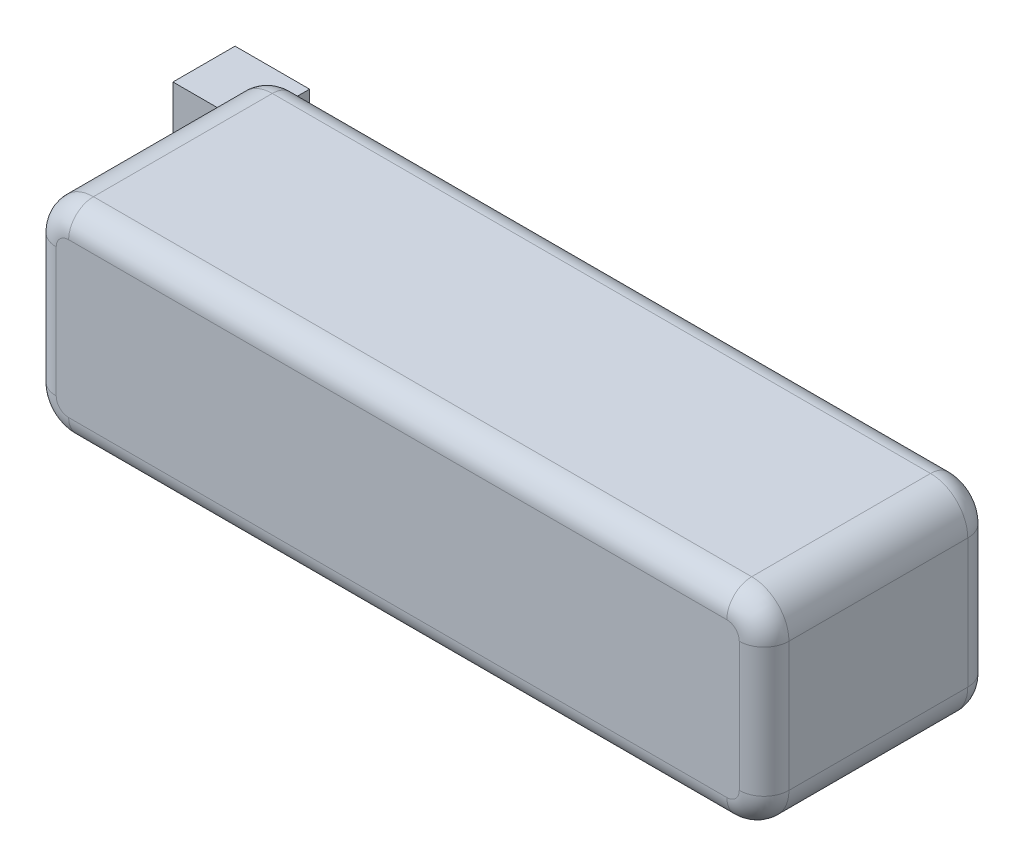
SolidWorks part; units mm, degrees
material "Polyurethane Foam Flexible"
ref_plane "Front Plane" through (0, 0, 0) normal (0, 0, 1) x (1, 0, 0)
ref_plane "Top Plane" through (0, 0, 0) normal (0, 1, 0) x (1, 0, 0)
ref_plane "Right Plane" through (0, 0, 0) normal (1, 0, 0) x (0, 0, -1)
sketch "Sketch1" plane through (0, 0, 0) normal (0, 1, 0) x (1, 0, 0)
  line L1 (0, 0) -> (74.93, 0)
  line L2 (0, 0) -> (0, -23.368)
  line L3 (0, -23.368) -> (74.93, -23.368)
  line L4 (74.93, 0) -> (74.93, -23.368)
  dimension "D1" = 74.93
  dimension "D2" = 23.368
extrude "Boss-Extrude1" add sketch "Sketch1" along normal blind 20.828
sketch "Sketch2" plane through (0, 0, 0) normal (-1, 0, 0) x (0, 0, 1)
  line L0 (0, 20.828) -> (0, 0) construction
  line L1 (0, 15.494) -> (1.27, 15.494)
  line L2 (0, 15.494) -> (0, 5.334)
  line L3 (0, 5.334) -> (1.27, 5.334)
  line L4 (1.27, 15.494) -> (1.27, 5.334)
  line L5 (3.34, 20.828) -> (3.34, 15.494) construction
  line L6 (0, 20.828) -> (23.368, 20.828) construction
  line L7 (3.34, 5.334) -> (3.34, 0) construction
  line L8 (0, 0) -> (23.368, 0) construction
  line L10 (0, 15.494) -> (-5.08, 15.494)
  line L11 (0, 15.494) -> (0, 5.334)
  line L12 (0, 5.334) -> (-5.08, 5.334)
  line L13 (-5.08, 15.494) -> (-5.08, 5.334)
  line M4 (0, 20.828) -> (0, 0)
  dimension "D1" = 10.16
  dimension "D2" = 5.08
  dimension "D3" = 1.27
extrude "Boss-Extrude2" add sketch "Sketch2" along normal blind 7.62 contours L10 L13 L12 M4 | L4 L1 L3 M4 region at (0, 10.414, 0.635) region at (0, 10.414, -2.54)
fillet "Fillet1" radius 2.54 2 edges at (0, 10.414, 1.27) (0, 10.414, 0)
fillet "Fillet2" radius 3.81 4 edges at (0, 20.828, 11.684) (74.93, 20.828, 11.684) (74.93, 0, 11.684) (0, 0, 11.684)
fillet "Fillet3" radius 2.54 8 edges at (1.1159, 1.1159, 23.368) (0, 10.414, 23.368) (1.1159, 19.7121, 23.368) (37.465, 20.828, 23.368) (73.8141, 19.7121, 23.368) (74.93, 10.414, 23.368) (73.8141, 1.1159, 23.368) (37.465, 0, 23.368)
fillet "Fillet4" radius 2.54 9 edges at (0, 16.256, 0) (1.1159, 19.7121, 0) (37.465, 20.828, 0) (73.8141, 19.7121, 0) (74.93, 10.414, 0) (73.8141, 1.1159, 0) (0, 4.572, 0) (1.1159, 1.1159, 0) (37.465, 0, 0)
